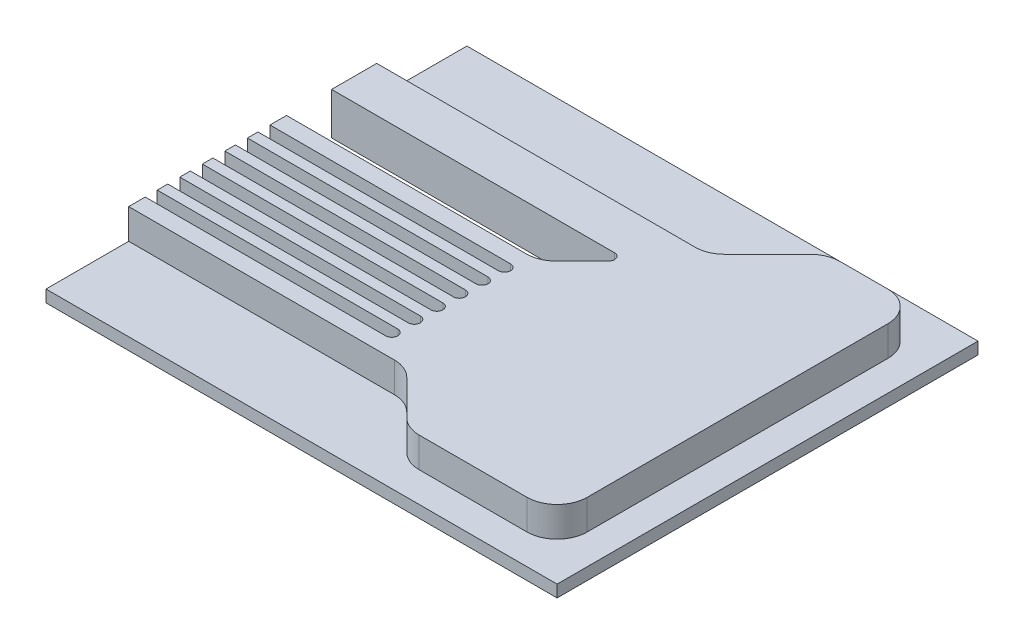
SolidWorks part; units mm, degrees
ref_plane "Front Plane" through (0, 0, 0) normal (0, 0, 1) x (1, 0, 0)
ref_plane "Top Plane" through (0, 0, 0) normal (0, 1, 0) x (1, 0, 0)
ref_plane "Right Plane" through (0, 0, 0) normal (1, 0, 0) x (0, 0, -1)
sketch "Sketch1" plane through (0, 0, 0) normal (0, 1, 0) x (1, 0, 0)
  line L1 (0, 0) -> (170, 0)
  line L2 (0, 0) -> (0, 140)
  line L3 (0, 140) -> (170, 140)
  line L4 (170, 0) -> (170, 140)
  dimension "D1" = 170
  dimension "D2" = 140
extrude "Boss-Extrude1" add sketch "Sketch1" along normal blind 4
sketch "Sketch2" plane through (0, 4, 0) normal (0, 1, 0) x (1, 0, 0)
  line L4 (112.9289, 112.9289) -> (127.0711, 127.0711)
  line L5 (134.1421, 130) -> (150, 130)
  line L6 (160, 120) -> (160, 20)
  line L12 (86.8495, 82.9289) -> (95.5064, 91.5858)
  line L13 (170, 0) -> (170, 140) construction
  line L14 (170, 140) -> (0, 140) construction
  line L15 (105.8579, 110) -> (0, 110)
  line L16 (0, 140) -> (0, 0) construction
  line L17 (94.0922, 95) -> (0, 95)
  line L18 (-80, 42.5) -> (80, 42.5) construction
  line L19 (0, 0) -> (170, 0) construction
  line L20 (150, 10) -> (114.1421, 10)
  line L21 (107.0711, 12.9289) -> (95.4289, 24.5711)
  line L22 (88.3579, 27.5) -> (0, 27.5)
  line L23 (-80, 44.5) -> (80, 44.5)
  line L26 (-80, 35) -> (80, 35) construction
  line L27 (-80, 37) -> (80, 37)
  line L28 (-80, 33) -> (80, 33)
  line L29 (-80, 40.5) -> (80, 40.5)
  line L32 (-80, 50) -> (80, 50) construction
  line L35 (-80, 52) -> (80, 52)
  line L38 (-80, 48) -> (80, 48)
  line L39 (0, 80) -> (30.447, 80)
  line L40 (30.447, 80) -> (79.7785, 80)
  line L41 (-80, 57.5) -> (80, 57.5) construction
  line L42 (-80, 59.5) -> (80, 59.5)
  line L43 (-80, 55.5) -> (80, 55.5)
  line L44 (80, 65) -> (-80, 65) construction
  line L45 (80, 63) -> (-80, 63)
  line L46 (80, 67) -> (-80, 67)
  line L47 (-80, 72.5) -> (80, 72.5) construction
  line L48 (-80, 74.5) -> (80, 74.5)
  line L49 (-80, 70.5) -> (80, 70.5)
  arc A2 (-80, 37) -> (-80, 33) centre (-80, 35) ccw
  arc A3 (80, 33) -> (80, 37) centre (80, 35) ccw
  arc A10 (150, 130) -> (160, 120) centre (150, 120) cw
  arc A11 (160, 20) -> (150, 10) centre (150, 20) cw
  arc A12 (-80, 44.5) -> (-80, 40.5) centre (-80, 42.5) ccw
  arc A13 (80, 40.5) -> (80, 44.5) centre (80, 42.5) ccw
  arc A14 (-80, 52) -> (-80, 48) centre (-80, 50) ccw
  arc A15 (80, 48) -> (80, 52) centre (80, 50) ccw
  arc A16 (-80, 59.5) -> (-80, 55.5) centre (-80, 57.5) ccw
  arc A17 (80, 55.5) -> (80, 59.5) centre (80, 57.5) ccw
  arc A18 (80, 63) -> (80, 67) centre (80, 65) ccw
  arc A19 (-80, 67) -> (-80, 63) centre (-80, 65) ccw
  arc A20 (-80, 74.5) -> (-80, 70.5) centre (-80, 72.5) ccw
  arc A21 (80, 70.5) -> (80, 74.5) centre (80, 72.5) ccw
  arc A22 (112.9289, 112.9289) -> (105.8579, 110) centre (105.8579, 120) cw
  arc A23 (127.0711, 127.0711) -> (134.1421, 130) centre (134.1421, 120) cw
  arc A24 (88.3579, 27.5) -> (95.4289, 24.5711) centre (88.3579, 17.5) cw
  arc A25 (107.0711, 12.9289) -> (114.1421, 10) centre (114.1421, 20) ccw
  arc A26 (95.5064, 91.5858) -> (94.0922, 95) centre (94.0922, 93) ccw
  arc A27 (86.8495, 82.9289) -> (79.7785, 80) centre (79.7785, 90) cw
  point P20 (0, 42.5)
  point P27 (0, 35)
  point P34 (0, 50)
  point P41 (0, 57.5)
  point P46 (0, 65)
  point P55 (160, 130)
  point P63 (0, 72.5)
  point P70 (110, 110)
  point P73 (130, 130)
  point P76 (92.5, 27.5)
  point P79 (110, 10)
  point P82 (98.9206, 95)
  point P85 (83.9206, 80)
  line M35 (0, 140) -> (0, 0)
  dimension "D1" = 10
  dimension "D4" = 10
  dimension "D22" = 2
  dimension "D25" = 2
  dimension "D26" = 2
  dimension "D27" = 2
  dimension "D41" = 2
  dimension "D42" = 10
  dimension "D38" = 2
  dimension "D43" = 2
  dimension "D44" = 10
  dimension "D2" = 10
  dimension "D3" = 10
  dimension "D5" = 50
  dimension "D6" = 30
  dimension "D7" = 135
  dimension "D8" = 110
  dimension "D9" = 98.9206
  dimension "D10" = 21.2132
  dimension "D11" = 15
  dimension "D12" = 15
  dimension "D13" = 135
  dimension "D14" = 20
  dimension "D15" = 92.5
  dimension "D16" = 17.5
  dimension "D17" = 10
  dimension "D18" = 30
  dimension "D19" = 27.5
  dimension "D20" = 35
  dimension "D21" = 35
  dimension "D23" = 160
  dimension "D24" = 92.5
  dimension "D28" = 160
  dimension "D29" = 160
  dimension "D30" = 160
  dimension "D31" = 42.5
  dimension "D32" = 50
  dimension "D33" = 0
  dimension "D34" = 0
  dimension "D35" = 57.5
  dimension "D36" = 65
  dimension "D37" = 72.5
  dimension "D39" = 5.5
  dimension "D40" = 0
extrude "Boss-Extrude2" add sketch "Sketch2" along normal blind 10 contours L12 A27 L40 L39 L48 A21 L49 L46 A18 L45 L42 A17 L43 L35 A15 L38 L23 A13 L29 L27 A3 L28 L22 A24 L21 A25 L20 A11 L6 A10 L5 A23 L4 A22 L15 L17 A26 M35
sketch "Sketch4" plane through (0, 0, 0) normal (0, 1, 0) x (1, 0, 0)
  line L4 (112.9289, 112.9289) -> (127.0711, 127.0711)
  line L5 (134.1421, 130) -> (150, 130)
  line L6 (160, 120) -> (160, 20)
  line L12 (86.8495, 82.9289) -> (95.5064, 91.5858)
  line L15 (105.8579, 110) -> (0, 110)
  line L17 (94.0922, 95) -> (0, 95)
  line L18 (-80, 42.5) -> (80, 42.5) construction
  line L20 (150, 10) -> (114.1421, 10)
  line L21 (107.0711, 12.9289) -> (95.4289, 24.5711)
  line L22 (88.3579, 27.5) -> (0, 27.5)
  line L23 (-80, 44.5) -> (80, 44.5)
  line L26 (-80, 35) -> (80, 35) construction
  line L27 (-80, 37) -> (80, 37)
  line L28 (-80, 33) -> (80, 33)
  line L29 (-80, 40.5) -> (80, 40.5)
  line L32 (-80, 50) -> (80, 50) construction
  line L35 (-80, 52) -> (80, 52)
  line L38 (-80, 48) -> (80, 48)
  line L39 (0, 80) -> (30.447, 80)
  line L40 (30.447, 80) -> (79.7785, 80)
  line L41 (-80, 57.5) -> (80, 57.5) construction
  line L42 (-80, 59.5) -> (80, 59.5)
  line L43 (-80, 55.5) -> (80, 55.5)
  line L44 (80, 65) -> (-80, 65) construction
  line L45 (80, 63) -> (-80, 63)
  line L46 (80, 67) -> (-80, 67)
  line L47 (-80, 72.5) -> (80, 72.5) construction
  line L48 (-80, 74.5) -> (80, 74.5)
  line L49 (-80, 70.5) -> (80, 70.5)
  arc A2 (-80, 37) -> (-80, 33) centre (-80, 35) ccw
  arc A3 (80, 33) -> (80, 37) centre (80, 35) ccw
  arc A10 (150, 130) -> (160, 120) centre (150, 120) cw
  arc A11 (160, 20) -> (150, 10) centre (150, 20) cw
  arc A12 (-80, 44.5) -> (-80, 40.5) centre (-80, 42.5) ccw
  arc A13 (80, 40.5) -> (80, 44.5) centre (80, 42.5) ccw
  arc A14 (-80, 52) -> (-80, 48) centre (-80, 50) ccw
  arc A15 (80, 48) -> (80, 52) centre (80, 50) ccw
  arc A16 (-80, 59.5) -> (-80, 55.5) centre (-80, 57.5) ccw
  arc A17 (80, 55.5) -> (80, 59.5) centre (80, 57.5) ccw
  arc A18 (80, 63) -> (80, 67) centre (80, 65) ccw
  arc A19 (-80, 67) -> (-80, 63) centre (-80, 65) ccw
  arc A20 (-80, 74.5) -> (-80, 70.5) centre (-80, 72.5) ccw
  arc A21 (80, 70.5) -> (80, 74.5) centre (80, 72.5) ccw
  arc A22 (112.9289, 112.9289) -> (105.8579, 110) centre (105.8579, 120) cw
  arc A23 (127.0711, 127.0711) -> (134.1421, 130) centre (134.1421, 120) cw
  arc A24 (88.3579, 27.5) -> (95.4289, 24.5711) centre (88.3579, 17.5) cw
  arc A25 (107.0711, 12.9289) -> (114.1421, 10) centre (114.1421, 20) ccw
  arc A26 (95.5064, 91.5858) -> (94.0922, 95) centre (94.0922, 93) ccw
  arc A27 (86.8495, 82.9289) -> (79.7785, 80) centre (79.7785, 90) cw
  point P20 (0, 42.5)
  point P27 (0, 35)
  point P34 (0, 50)
  point P41 (0, 57.5)
  point P46 (0, 65)
  point P55 (160, 130)
  point P63 (0, 72.5)
  point P70 (110, 110)
  point P73 (130, 130)
  point P76 (92.5, 27.5)
  point P79 (110, 10)
  point P82 (98.9206, 95)
  point P85 (83.9206, 80)
  dimension "D1" = 10
  dimension "D4" = 10
  dimension "D22" = 2
  dimension "D25" = 2
  dimension "D26" = 2
  dimension "D27" = 2
  dimension "D41" = 2
  dimension "D42" = 10
  dimension "D38" = 2
  dimension "D43" = 2
  dimension "D44" = 10
  dimension "D5" = 50
  dimension "D6" = 30
  dimension "D7" = 135
  dimension "D8" = 110
  dimension "D9" = 98.9206
  dimension "D10" = 21.2132
  dimension "D11" = 15
  dimension "D12" = 15
  dimension "D13" = 135
  dimension "D14" = 20
  dimension "D15" = 92.5
  dimension "D16" = 17.5
  dimension "D23" = 160
  dimension "D24" = 92.5
  dimension "D28" = 160
  dimension "D29" = 160
  dimension "D30" = 160
  dimension "D39" = 5.5
extrude "Cut-Extrude3" cut sketch "Sketch4" against normal through all both and the other way through all contours L39 L40 A27 L12 A26 L17
sketch "Sketch5" plane through (0, 0, 0) normal (0, 1, 0) x (1, 0, 0)
  line L4 (112.9289, 112.9289) -> (127.0711, 127.0711)
  line L5 (134.1421, 130) -> (150, 130)
  line L6 (160, 120) -> (160, 20)
  line L12 (86.8495, 82.9289) -> (95.5064, 91.5858)
  line L15 (105.8579, 110) -> (0, 110)
  line L17 (94.0922, 95) -> (0, 95)
  line L18 (-80, 42.5) -> (80, 42.5) construction
  line L20 (150, 10) -> (114.1421, 10)
  line L21 (107.0711, 12.9289) -> (95.4289, 24.5711)
  line L22 (88.3579, 27.5) -> (0, 27.5)
  line L23 (-80, 44.5) -> (80, 44.5)
  line L26 (-80, 35) -> (80, 35) construction
  line L27 (-80, 37) -> (80, 37)
  line L28 (-80, 33) -> (80, 33)
  line L29 (-80, 40.5) -> (80, 40.5)
  line L32 (-80, 50) -> (80, 50) construction
  line L35 (-80, 52) -> (80, 52)
  line L38 (-80, 48) -> (80, 48)
  line L39 (0, 80) -> (30.447, 80)
  line L40 (30.447, 80) -> (79.7785, 80)
  line L41 (-80, 57.5) -> (80, 57.5) construction
  line L42 (-80, 59.5) -> (80, 59.5)
  line L43 (-80, 55.5) -> (80, 55.5)
  line L44 (80, 65) -> (-80, 65) construction
  line L45 (80, 63) -> (-80, 63)
  line L46 (80, 67) -> (-80, 67)
  line L47 (-80, 72.5) -> (80, 72.5) construction
  line L48 (-80, 74.5) -> (80, 74.5)
  line L49 (-80, 70.5) -> (80, 70.5)
  arc A2 (-80, 37) -> (-80, 33) centre (-80, 35) ccw
  arc A3 (80, 33) -> (80, 37) centre (80, 35) ccw
  arc A10 (150, 130) -> (160, 120) centre (150, 120) cw
  arc A11 (160, 20) -> (150, 10) centre (150, 20) cw
  arc A12 (-80, 44.5) -> (-80, 40.5) centre (-80, 42.5) ccw
  arc A13 (80, 40.5) -> (80, 44.5) centre (80, 42.5) ccw
  arc A14 (-80, 52) -> (-80, 48) centre (-80, 50) ccw
  arc A15 (80, 48) -> (80, 52) centre (80, 50) ccw
  arc A16 (-80, 59.5) -> (-80, 55.5) centre (-80, 57.5) ccw
  arc A17 (80, 55.5) -> (80, 59.5) centre (80, 57.5) ccw
  arc A18 (80, 63) -> (80, 67) centre (80, 65) ccw
  arc A19 (-80, 67) -> (-80, 63) centre (-80, 65) ccw
  arc A20 (-80, 74.5) -> (-80, 70.5) centre (-80, 72.5) ccw
  arc A21 (80, 70.5) -> (80, 74.5) centre (80, 72.5) ccw
  arc A22 (112.9289, 112.9289) -> (105.8579, 110) centre (105.8579, 120) cw
  arc A23 (127.0711, 127.0711) -> (134.1421, 130) centre (134.1421, 120) cw
  arc A24 (88.3579, 27.5) -> (95.4289, 24.5711) centre (88.3579, 17.5) cw
  arc A25 (107.0711, 12.9289) -> (114.1421, 10) centre (114.1421, 20) ccw
  arc A26 (95.5064, 91.5858) -> (94.0922, 95) centre (94.0922, 93) ccw
  arc A27 (86.8495, 82.9289) -> (79.7785, 80) centre (79.7785, 90) cw
  point P20 (0, 42.5)
  point P27 (0, 35)
  point P34 (0, 50)
  point P41 (0, 57.5)
  point P46 (0, 65)
  point P55 (160, 130)
  point P63 (0, 72.5)
  point P70 (110, 110)
  point P73 (130, 130)
  point P76 (92.5, 27.5)
  point P79 (110, 10)
  point P82 (98.9206, 95)
  point P85 (83.9206, 80)
  dimension "D1" = 10
  dimension "D4" = 10
  dimension "D22" = 2
  dimension "D25" = 2
  dimension "D26" = 2
  dimension "D27" = 2
  dimension "D41" = 2
  dimension "D42" = 10
  dimension "D38" = 2
  dimension "D43" = 2
  dimension "D44" = 10
  dimension "D5" = 50
  dimension "D6" = 30
  dimension "D7" = 135
  dimension "D8" = 110
  dimension "D9" = 98.9206
  dimension "D10" = 21.2132
  dimension "D11" = 15
  dimension "D12" = 15
  dimension "D13" = 135
  dimension "D14" = 20
  dimension "D15" = 92.5
  dimension "D16" = 17.5
  dimension "D23" = 160
  dimension "D24" = 92.5
  dimension "D28" = 160
  dimension "D29" = 160
  dimension "D30" = 160
  dimension "D39" = 5.5
extrude "Cut-Extrude6" cut sketch "Sketch5" along normal blind 10 contours L49 A21 L48 A20 | L45 A19 L46 A18 | L43 A17 L42 A16 | L38 A15 L35 A14 | L29 A13 L23 A12 | L28 A3 L27 A2
